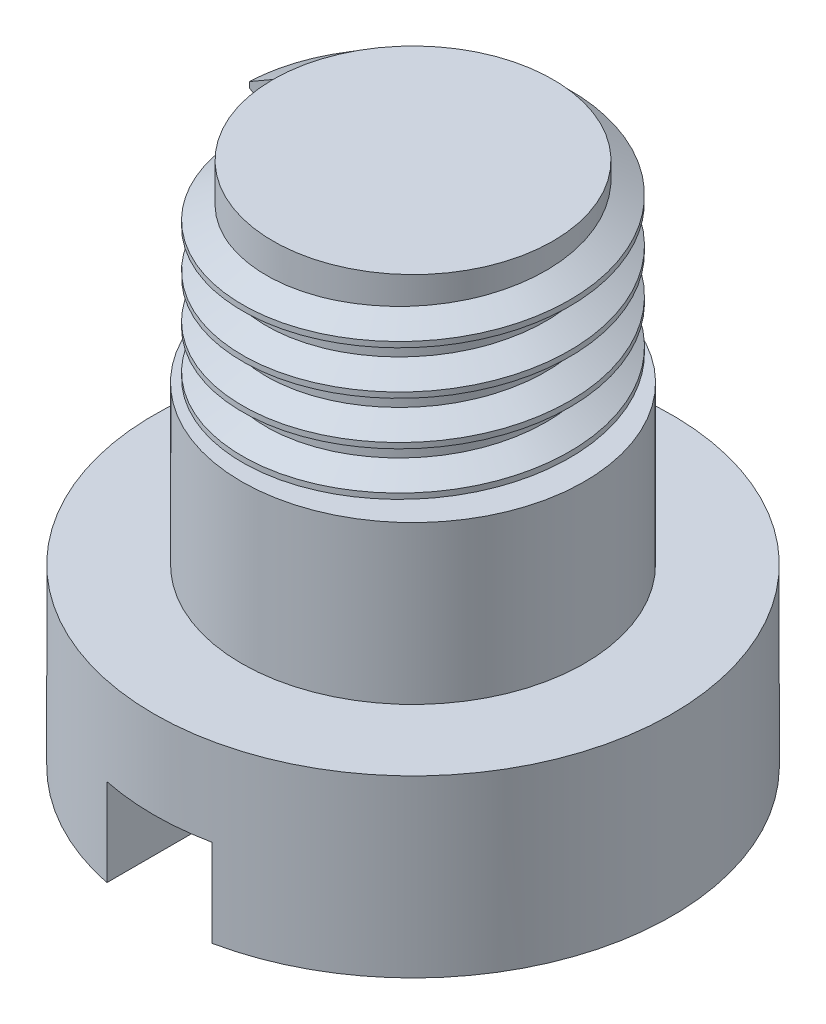
SolidWorks part; units mm, degrees
ref_plane "Front Plane" through (0, 0, 0) normal (0, 0, 1) x (1, 0, 0)
ref_plane "Top Plane" through (0, 0, 0) normal (0, 1, 0) x (1, 0, 0)
ref_plane "Right Plane" through (0, 0, 0) normal (1, 0, 0) x (0, 0, -1)
sketch "Sketch1" plane through (0, 0, 0) normal (0, 1, 0) x (1, 0, 0)
  circle A0 centre (0, 0) radius 7.4
  dimension "D1" = 14.8
extrude "Boss-Extrude1" add sketch "Sketch1" along normal blind 5
sketch "Sketch2" plane through (0, 5, 0) normal (0, 1, 0) x (1, 0, 0)
  circle A0 centre (0, 0) radius 4.9
  dimension "D1" = 9.8
extrude "Boss-Extrude2" add sketch "Sketch2" along normal blind 10
sketch "Sketch5" plane through (0, 0, 0) normal (0, -1, 0) x (1, 0, 0)
  line L1 (-1.5, -7.4) -> (1.5, -7.4)
  line L2 (-1.5, -7.4) -> (-1.5, 7.4)
  line L3 (-1.5, 7.4) -> (1.5, 7.4)
  line L4 (1.5, -7.4) -> (1.5, 7.4)
  circle A0 centre (0, 0) radius 7.4 construction
  point P4 (0, 7.4)
  point P9 (0, -7.4)
  dimension "D1" = 14.8
  dimension "D2" = 3
sketch "Sketch13" plane through (0, 15, 0) normal (0, 1, 0) x (1, 0, 0)
  circle A0 centre (0, 0) radius 4
  dimension "D1" = 8
extrude "Cut-Extrude4" cut sketch "Sketch13" against normal blind 5.5 flip side to cut
thread "Thread2" pitch 1.25 method extrude trim with end face yes profile "Thread Profile4" start angle 0, offset 0, length 0, pitch 1.25, diameter 8
ref_plane "Plane4" through (-4, 15, 0) normal (0, 0, 1) x (-1, 0, 0)
sketch "Thread Profile4" plane through (-4, 15, 0) normal (0, 0, 1) x (-1, 0, 0)
  line L0 (0, 0) -> (0, 1.25) construction
  line L1 (0, 0) -> (0.6766, 0.3906)
  line L2 (0.6766, 0.3906) -> (0.6766, 0.5469)
  line L3 (0.6766, 0.5469) -> (0, 0.9375)
  line L4 (0.6766, 0.4687) -> (0, 0.4687) construction
  line L11 (0, 0) -> (0, 0.9375)
  point P2 (0, 0)
  dimension "Pitch" = 1.25
  dimension "Profile_Angle" = 60
  dimension "Profile_Land" = 0.1562
  dimension "Profile_Height" = 0.6766
extrude "Cut-Extrude5" cut sketch "Sketch5" against normal blind 2.5
